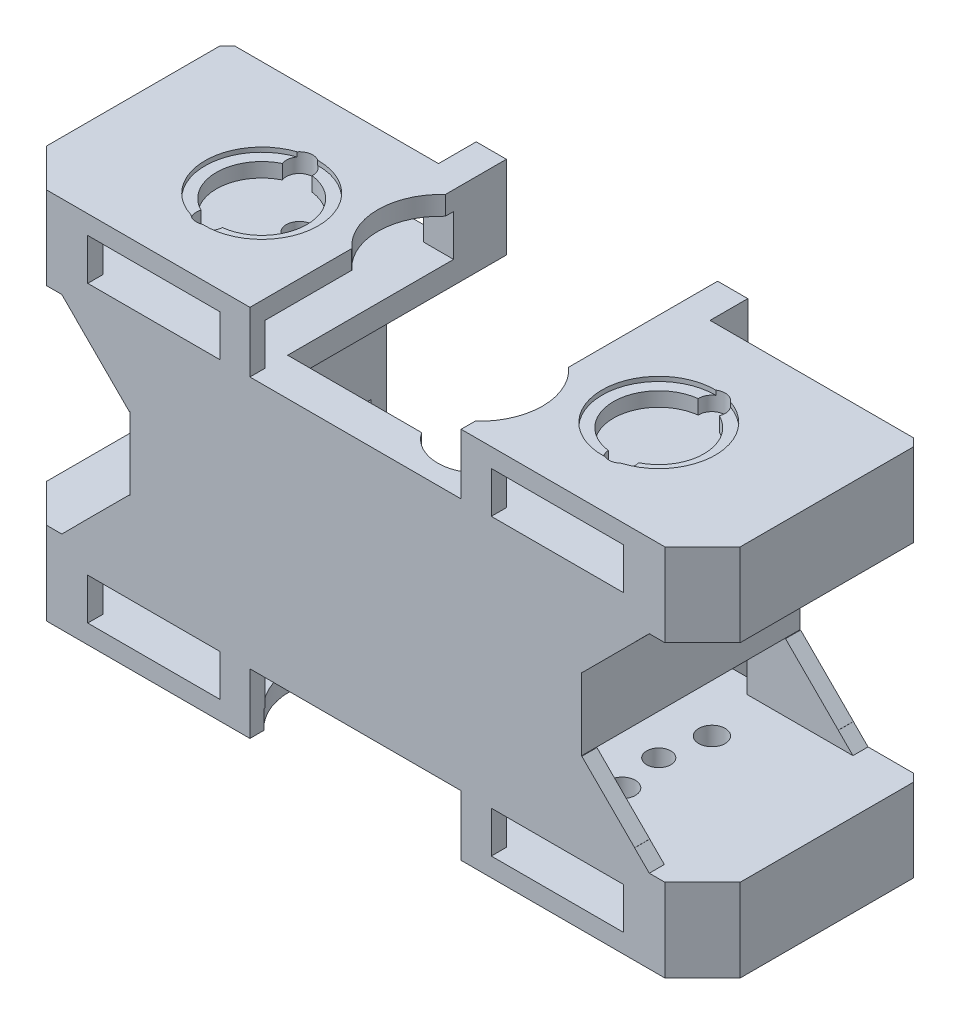
SolidWorks part; units mm, degrees
ref_plane "正面" through (0, 0, 0) normal (0, 0, 1) x (1, 0, 0)
ref_plane "平面" through (0, 0, 0) normal (0, 1, 0) x (1, 0, 0)
ref_plane "右側面" through (0, 0, 0) normal (1, 0, 0) x (0, 0, -1)
sketch "Sketch1" plane through (0, 0, 0) normal (0, 0, 1) x (1, 0, 0)
  line L0 (2.2, -4.75) -> (-2.2, -4.75) construction
  line L2 (-37, 13.75) -> (37, 13.75)
  line L3 (37, -13.75) -> (-37, -13.75)
  line L4 (30.8552, 0) -> (-45.9764, 0) construction
  line L5 (37, -4.795) -> (24.925, -4.795)
  line L6 (24.925, -4.795) -> (24.925, 4.795)
  line L7 (37, 4.795) -> (24.925, 4.795)
  line L8 (0, -7.712) -> (0, 34.8193) construction
  line L11 (-2.2, -4.75) -> (-2.2, 4.75) construction
  line L13 (2.2, -4.75) -> (2.2, 4.75) construction
  line L16 (2.2, 1.8709) -> (2.2, 4.75) construction
  line L17 (2.2, 1.8709) -> (2.2, 4.75) construction
  line L18 (-37, -13.75) -> (-37, -4.795)
  line L22 (-37, 4.795) -> (-24.925, 4.795)
  line L23 (-24.925, -4.795) -> (-24.925, 4.795)
  line L24 (-37, -4.795) -> (-24.925, -4.795)
  line L25 (-37, 4.795) -> (-37, 13.75)
  line L28 (37, 4.795) -> (37, 13.75)
  line L29 (37, -13.75) -> (37, -4.795)
  line L30 (2.2, 4.75) -> (-2.2, 4.75) construction
  point P2 (-2.2, 1.8709)
  point P8 (24.925, 0)
  point P33 (-24.925, 0)
  dimension "D1" = 27.5
  dimension "D2" = 37
  dimension "D3" = 2.2
  dimension "D4" = 4.4
  dimension "D5" = 9.5
extrude "Boss-Extrude1" add sketch "Sketch1" along normal blind 2
sketch "Sketch2" plane through (0, 0, 0) normal (0, 0, -1) x (-1, 0, 0)
  line L0 (-2.2, -4.75) -> (2.2, -4.75) construction
  line L1 (-2.2, -4.75) -> (-2.2, 4.75) construction
  line L2 (-2.2, 4.75) -> (2.2, 4.75) construction
  line L3 (2.2, -4.75) -> (2.2, 4.75) construction
  line L4 (-2.2, -4.75) -> (2.2, -4.75)
  line L5 (-2.2, -4.75) -> (-2.2, 4.75)
  line L6 (-2.2, 4.75) -> (2.2, 4.75)
  line L7 (2.2, -4.75) -> (2.2, 4.75)
  line L8 (37, -4.795) -> (24.925, -4.795) construction
  line L9 (24.925, -4.795) -> (24.925, 4.795) construction
  line L10 (37, 4.795) -> (24.925, 4.795) construction
  line L11 (-37, -4.795) -> (-24.925, -4.795) construction
  line L12 (-24.925, -4.795) -> (-24.925, 4.795) construction
  line L13 (-37, 4.795) -> (-24.925, 4.795) construction
  line L14 (29.925, -4.795) -> (24.925, -4.795)
  line L15 (24.925, -4.795) -> (24.925, 4.795)
  line L16 (29.925, 4.795) -> (24.925, 4.795)
  line L17 (-29.925, -4.795) -> (-24.925, -4.795)
  line L18 (-24.925, -4.795) -> (-24.925, 4.795)
  line L19 (-29.925, 4.795) -> (-24.925, 4.795)
  line L20 (-29.925, 4.795) -> (-29.925, -4.795)
  line L21 (0, -7.712) -> (0, 34.8193) construction
  line L22 (0, -7.712) -> (0, 34.8193) construction
  line L23 (29.925, 4.795) -> (29.925, -4.795)
  dimension "D1" = 5
extrude "Boss-Extrude2" add sketch "Sketch2" along normal blind 25 and the other way blind 2
sketch "Sketch3" plane through (0, 0, 2) normal (0, 0, 1) x (1, 0, 0)
  line L0 (0, -63.6478) -> (0, 57.6808) construction
  line L1 (54.2453, 0) -> (-65.9985, 0) construction
  line L11 (-37, 11.75) -> (-37, 24.75)
  line L12 (-37, 24.75) -> (-14, 24.75)
  line L13 (-14, 24.75) -> (-14, 11.75)
  line L14 (-14, 11.75) -> (-37, 11.75)
  line L19 (-37, 4.795) -> (-37, 13.75) construction
  line L20 (-37, 13.75) -> (37, 13.75) construction
  line L21 (14, 11.75) -> (37, 11.75)
  line L22 (14, 24.75) -> (14, 11.75)
  line L23 (37, 24.75) -> (14, 24.75)
  line L24 (37, 11.75) -> (37, 24.75)
  line L25 (37, -11.75) -> (37, -24.75)
  line L26 (37, -24.75) -> (14, -24.75)
  line L27 (14, -24.75) -> (14, -11.75)
  line L28 (14, -11.75) -> (37, -11.75)
  line L29 (-14, -11.75) -> (-37, -11.75)
  line L30 (-14, -24.75) -> (-14, -11.75)
  line L31 (-37, -24.75) -> (-14, -24.75)
  line L32 (-37, -11.75) -> (-37, -24.75)
  line L33 (-35.5, 22.25) -> (-18, 22.25)
  line L34 (-18, 22.25) -> (-18, 15.75)
  line L35 (-18, 15.75) -> (-35.5, 15.75)
  line L36 (-35.5, 15.75) -> (-35.5, 22.25)
  line L37 (35.5, 15.75) -> (35.5, 22.25)
  line L38 (18, 15.75) -> (35.5, 15.75)
  line L39 (18, 22.25) -> (18, 15.75)
  line L40 (35.5, 22.25) -> (18, 22.25)
  line L41 (35.5, -22.25) -> (18, -22.25)
  line L42 (18, -22.25) -> (18, -15.75)
  line L43 (18, -15.75) -> (35.5, -15.75)
  line L44 (35.5, -15.75) -> (35.5, -22.25)
  line L45 (-35.5, -15.75) -> (-35.5, -22.25)
  line L46 (-18, -15.75) -> (-35.5, -15.75)
  line L47 (-18, -22.25) -> (-18, -15.75)
  line L48 (-35.5, -22.25) -> (-18, -22.25)
  dimension "D1" = 2
  dimension "D2" = 13
  dimension "D3" = 23
  dimension "D4" = 2.5
  dimension "D5" = 4
  dimension "D6" = 4
  dimension "D7" = 1.5
extrude "Boss-Extrude3" add sketch "Sketch3" against normal blind 2
chamfer "Chamfer4" [suppressed] distance 2 angle 45
sketch "Sketch4" plane through (0, 0, 2) normal (0, 0, 1) x (1, 0, 0)
  line L0 (30.8552, 0) -> (-45.9764, 0) construction
  line L1 (0, -7.712) -> (0, 34.8193) construction
  line L2 (30.8552, 0) -> (-45.9764, 0) construction
  line L3 (0, -7.712) -> (0, 34.8193) construction
  line L4 (37, 24.75) -> (14, 24.75)
  line L5 (14, 24.75) -> (14, 22.25)
  line L6 (14, 22.25) -> (37, 22.25)
  line L7 (37, 4.795) -> (37, 24.75) construction
  line L9 (14, 13.75) -> (14, 16.75)
  line L10 (14, 24.75) -> (14, 13.75) construction
  line L12 (-46, 16.75) -> (-46, 13.75)
  line L13 (46, 16.75) -> (46, 13.75)
  line L14 (14, 16.75) -> (46, 16.75)
  line L15 (-14, 13.75) -> (-14, 16.75)
  line L17 (-14, 22.25) -> (-37, 22.25)
  line L18 (-14, 24.75) -> (-14, 22.25)
  line L19 (-37, 24.75) -> (-14, 24.75)
  line L20 (-14, 13.75) -> (-14, 24.75) construction
  line L21 (37, 22.25) -> (37, 24.75)
  line L22 (-37, 22.25) -> (-37, 24.75)
  line L23 (-37, -22.25) -> (-37, -24.75)
  line L24 (37, -22.25) -> (37, -24.75)
  line L25 (-37, -24.75) -> (-14, -24.75)
  line L26 (-14, -24.75) -> (-14, -22.25)
  line L27 (-14, -22.25) -> (-37, -22.25)
  line L29 (-14, -13.75) -> (-14, -16.75)
  line L30 (14, -16.75) -> (46, -16.75)
  line L31 (46, -16.75) -> (46, -13.75)
  line L32 (-46, -16.75) -> (-46, -13.75)
  line L33 (-14, -16.75) -> (-46, -16.75)
  line L34 (14, -13.75) -> (14, -16.75)
  line L36 (14, -22.25) -> (37, -22.25)
  line L37 (14, -24.75) -> (14, -22.25)
  line L38 (37, -24.75) -> (14, -24.75)
  line L39 (-14, 16.75) -> (-46, 16.75)
  line L40 (-46, 13.75) -> (-14, 13.75)
  line L41 (-46, -13.75) -> (-14, -13.75)
  line L42 (14, -13.75) -> (46, -13.75)
  line L43 (14, 13.75) -> (46, 13.75)
  dimension "D1" = 32
  dimension "D2" = 3
  dimension "D3" = 2.5
extrude "Boss-Extrude4" add sketch "Sketch4" against normal blind 27
sketch "Sketch5" plane through (0, 0, -25) normal (0, 0, -1) x (-1, 0, 0)
  line L85 (14, -13.75) -> (14, -24.75)
  line L86 (-14, -13.75) -> (14, -13.75)
  line L87 (-14, -24.75) -> (-14, -13.75)
  line L88 (-37, -24.75) -> (-14, -24.75)
  line L89 (-37, -16.75) -> (-37, -24.75)
  line L90 (-29.925, -4.795) -> (-37, -4.795)
  line L91 (-29.925, 4.795) -> (-29.925, -4.795)
  line L92 (-37, 4.795) -> (-29.925, 4.795)
  line L93 (-37, 13.75) -> (-37, 4.795)
  line L94 (-14, 24.75) -> (-37, 24.75)
  line L95 (-14, 13.75) -> (-14, 24.75)
  line L96 (14, 13.75) -> (-14, 13.75)
  line L97 (14, 24.75) -> (14, 13.75)
  line L98 (37, 24.75) -> (14, 24.75)
  line L99 (37, 16.75) -> (37, 24.75)
  line L100 (29.925, 4.795) -> (37, 4.795)
  line L101 (29.925, -4.795) -> (29.925, 4.795)
  line L102 (37, -4.795) -> (29.925, -4.795)
  line L103 (37, -13.75) -> (37, -4.795)
  line L104 (14, -24.75) -> (37, -24.75)
  line L105 (14, -13.75) -> (14, -24.75)
  line L106 (-14, -13.75) -> (14, -13.75)
  line L107 (-14, -24.75) -> (-14, -13.75)
  line L108 (-37, -24.75) -> (-14, -24.75)
  line L109 (-37, -16.75) -> (-37, -24.75)
  line L110 (-29.925, -4.795) -> (-37, -4.795)
  line L111 (-29.925, 4.795) -> (-29.925, -4.795)
  line L112 (-37, 4.795) -> (-29.925, 4.795)
  line L113 (-37, 13.75) -> (-37, 4.795)
  line L114 (-14, 24.75) -> (-37, 24.75)
  line L115 (-14, 13.75) -> (-14, 24.75)
  line L116 (14, 13.75) -> (-14, 13.75)
  line L117 (14, 24.75) -> (14, 13.75)
  line L118 (37, 24.75) -> (14, 24.75)
  line L119 (37, 16.75) -> (37, 24.75)
  line L120 (29.925, 4.795) -> (37, 4.795)
  line L121 (29.925, -4.795) -> (29.925, 4.795)
  line L122 (37, -4.795) -> (29.925, -4.795)
  line L123 (37, -13.75) -> (37, -4.795)
  line L124 (14, -24.75) -> (37, -24.75)
  line L141 (-46, -16.75) -> (-37, -16.75)
  line L142 (-46, -16.75) -> (-37, -16.75)
  line L143 (-46, -13.75) -> (-46, -16.75)
  line L144 (-46, -13.75) -> (-46, -16.75)
  line L145 (-37, -13.75) -> (-46, -13.75)
  line L146 (-37, -13.75) -> (-46, -13.75)
  line L147 (-37, -4.795) -> (-37, -13.75)
  line L148 (-37, -4.795) -> (-37, -13.75)
  line L149 (-46, 13.75) -> (-37, 13.75)
  line L150 (-46, 13.75) -> (-37, 13.75)
  line L151 (-46, 16.75) -> (-46, 13.75)
  line L152 (-46, 16.75) -> (-46, 13.75)
  line L153 (-37, 16.75) -> (-46, 16.75)
  line L154 (-37, 16.75) -> (-46, 16.75)
  line L155 (-37, 24.75) -> (-37, 16.75)
  line L156 (-37, 24.75) -> (-37, 16.75)
  line L157 (46, 16.75) -> (37, 16.75)
  line L158 (46, 16.75) -> (37, 16.75)
  line L159 (46, 13.75) -> (46, 16.75)
  line L160 (46, 13.75) -> (46, 16.75)
  line L161 (37, 13.75) -> (46, 13.75)
  line L162 (37, 13.75) -> (46, 13.75)
  line L163 (37, 4.795) -> (37, 13.75)
  line L164 (37, 4.795) -> (37, 13.75)
  line L165 (46, -13.75) -> (37, -13.75)
  line L166 (46, -13.75) -> (37, -13.75)
  line L167 (46, -16.75) -> (46, -13.75)
  line L168 (46, -16.75) -> (46, -13.75)
  line L169 (37, -16.75) -> (46, -16.75)
  line L170 (37, -16.75) -> (46, -16.75)
  line L171 (37, -24.75) -> (37, -16.75)
  line L172 (37, -24.75) -> (37, -16.75)
  dimension "D1" = 0
extrude "Boss-Extrude5" add sketch "Sketch5" along normal blind 2
chamfer "Chamfer5" distance 5 angle 45 4 edges at (46, -15.25, 2) (46, 15.25, 2) (-46, -15.25, 2) (-46, 15.25, 2)
chamfer "Chamfer6" distance 7 angle 45 8 edges at (-37, 4.795, 1) (-37, -4.795, 1) (-37, -4.795, -26) (-37, 4.795, -26) (37, 4.795, -26) (37, -4.795, -26) (37, -4.795, 1) (37, 4.795, 1)
sketch "Sketch6" plane through (0, 16.75, 0) normal (0, 1, 0) x (1, 0, 0)
  line L2 (-46, 27) -> (-46, 3) construction
  line L3 (-46, 27) -> (-37, 27) construction
  line L4 (-37, 0) -> (-37, -2)
  line L6 (-46, 27) -> (-46, 3)
  line L7 (-46, 27) -> (-37, 27)
  line L9 (-37, 27) -> (-37, 25)
  line L10 (-37, 25) -> (-44, 25)
  line L11 (-44, 25) -> (-44, 3.8284)
  line L13 (0, 37.9752) -> (0, -9.1121) construction
  line L22 (-46, 3) -> (-41, -2)
  line L23 (-41, -2) -> (-37, -2)
  line L25 (-44, 3.8284) -> (-40.1716, 0)
  line L26 (-40.1716, 0) -> (-37, 0)
  line L27 (-37, 0) -> (-35.5, 0) construction
  line L38 (-37, 27) -> (-37, -2) construction
  line L39 (40.1716, 0) -> (37, 0)
  line L40 (44, 3.8284) -> (40.1716, 0)
  line L41 (41, -2) -> (37, -2)
  line L42 (46, 3) -> (41, -2)
  line L43 (44, 25) -> (44, 3.8284)
  line L44 (37, 25) -> (44, 25)
  line L45 (37, 27) -> (37, 25)
  line L46 (46, 27) -> (37, 27)
  line L47 (46, 27) -> (46, 3)
  line L48 (37, 0) -> (37, -2)
  dimension "D1" = 2
  dimension "D2" = 2
  dimension "D3" = 2
extrude "Boss-Extrude6" add sketch "Sketch6" along normal up to surface (5.5 mm away) up to face at (-26.125, 22.25, -5.75)
sketch "Sketch7" plane through (0, 22.25, 0) normal (0, 1, 0) x (1, 0, 0)
  line L1 (-46, 3) -> (-46, 27) construction
  line L2 (-46, 27) -> (-37, 27) construction
  line L3 (-37, 27) -> (-37, -2) construction
  line L9 (-46, 3) -> (-46, 27)
  line L10 (-46, 27) -> (-37, 27)
  line L11 (-37, 27) -> (-37, -2)
  line L16 (-41, -2) -> (-37, -2) construction
  line L17 (-46, 3) -> (-41, -2) construction
  line L18 (-41, -2) -> (-37, -2)
  line L19 (-46, 3) -> (-41, -2)
  line L20 (0, 40.7113) -> (0, -15.6848) construction
  line L21 (46, 3) -> (41, -2)
  line L22 (41, -2) -> (37, -2)
  line L23 (37, 27) -> (37, -2)
  line L24 (46, 27) -> (37, 27)
  line L25 (46, 3) -> (46, 27)
extrude "Boss-Extrude7" add sketch "Sketch7" along normal up to surface (2.5 mm away) up to face at (-25.5, 24.75, -12.5)
sketch "Sketch8" plane through (0, 0, -25) normal (0, 0, 1) x (1, 0, 0)
  line L3 (-18, 16.75) -> (-18, 22.25)
  line L4 (-14, 16.75) -> (-14, 22.25)
  line L5 (-14, 22.25) -> (-44, 22.25)
  line L6 (-44, 22.25) -> (-44, 16.75)
  line L7 (-44, 16.75) -> (-14, 16.75)
  line L9 (-18, 22.25) -> (-44, 22.25)
  line L10 (-44, 22.25) -> (-44, 16.75)
  line L11 (-44, 16.75) -> (-18, 16.75)
  line L12 (14, 16.75) -> (44, 16.75)
  line L13 (44, 16.75) -> (44, 22.25)
  line L14 (44, 22.25) -> (14, 22.25)
  line L15 (14, 22.25) -> (14, 16.75)
  line L16 (18, 16.75) -> (44, 16.75)
  line L17 (44, 16.75) -> (44, 22.25)
  line L18 (44, 22.25) -> (18, 22.25)
  line L20 (18, 22.25) -> (18, 16.75)
  line L21 (18, 22.25) -> (18, 16.75) construction
  line L22 (30.8552, 0) -> (-45.9764, 0) construction
  line L23 (30.8552, 0) -> (-45.9764, 0) construction
  dimension "D1" = 0
  dimension "D2" = 0
extrude "Cut-Extrude1" cut sketch "Sketch8" against normal through all
sketch "Sketch9" plane through (0, -16.75, 0) normal (0, -1, 0) x (1, 0, 0)
  line L10 (41, 2) -> (37, 2)
  line L11 (37, 2) -> (37, 0)
  line L12 (37, 0) -> (40.1716, 0)
  line L13 (40.1716, 0) -> (44, -3.8284)
  line L14 (44, -3.8284) -> (44, -25)
  line L15 (44, -25) -> (37, -25)
  line L16 (37, -25) -> (37, -27)
  line L17 (37, -27) -> (46, -27)
  line L18 (46, -27) -> (46, -3)
  line L19 (46, -3) -> (41, 2)
  line L20 (41, 2) -> (37, 2)
  line L21 (37, 2) -> (37, 0)
  line L22 (37, 0) -> (40.1716, 0)
  line L23 (40.1716, 0) -> (44, -3.8284)
  line L24 (44, -3.8284) -> (44, -25)
  line L25 (44, -25) -> (37, -25)
  line L26 (37, -25) -> (37, -27)
  line L27 (37, -27) -> (46, -27)
  line L28 (46, -27) -> (46, -3)
  line L29 (46, -3) -> (41, 2)
  line L30 (-41, 2) -> (-46, -3)
  line L31 (-46, -3) -> (-46, -27)
  line L32 (-46, -27) -> (-37, -27)
  line L33 (-37, -27) -> (-37, -25)
  line L34 (-37, -25) -> (-44, -25)
  line L35 (-44, -25) -> (-44, -3.8284)
  line L36 (-44, -3.8284) -> (-40.1716, 0)
  line L37 (-40.1716, 0) -> (-37, 0)
  line L38 (-37, 0) -> (-37, 2)
  line L39 (-37, 2) -> (-41, 2)
  line L40 (-41, 2) -> (-46, -3)
  line L41 (-46, -3) -> (-46, -27)
  line L42 (-46, -27) -> (-37, -27)
  line L43 (-37, -27) -> (-37, -25)
  line L44 (-37, -25) -> (-44, -25)
  line L45 (-44, -25) -> (-44, -3.8284)
  line L46 (-44, -3.8284) -> (-40.1716, 0)
  line L47 (-40.1716, 0) -> (-37, 0)
  line L48 (-37, 0) -> (-37, 2)
  line L49 (-37, 2) -> (-41, 2)
  dimension "D1" = 0
  dimension "D2" = 0
extrude "Boss-Extrude8" add sketch "Sketch9" along normal up to surface (5.5 mm away) up to face at (26.125, -22.25, -5.75)
sketch "Sketch10" plane through (0, -22.25, 0) normal (0, -1, 0) x (1, 0, 0)
  line L5 (46, -3) -> (41, 2)
  line L6 (41, 2) -> (37, 2)
  line L7 (37, 2) -> (37, -27)
  line L8 (37, -27) -> (46, -27)
  line L9 (46, -27) -> (46, -3)
  line L10 (46, -3) -> (41, 2)
  line L11 (41, 2) -> (37, 2)
  line L12 (37, 2) -> (37, -27)
  line L13 (37, -27) -> (46, -27)
  line L14 (46, -27) -> (46, -3)
  line L15 (-46, -3) -> (-46, -27)
  line L16 (-46, -27) -> (-37, -27)
  line L17 (-37, -27) -> (-37, 2)
  line L18 (-37, 2) -> (-41, 2)
  line L19 (-41, 2) -> (-46, -3)
  line L20 (-46, -3) -> (-46, -27)
  line L21 (-46, -27) -> (-37, -27)
  line L22 (-37, -27) -> (-37, 2)
  line L23 (-37, 2) -> (-41, 2)
  line L24 (-41, 2) -> (-46, -3)
  dimension "D1" = 0
  dimension "D2" = 0
extrude "Boss-Extrude9" add sketch "Sketch10" along normal up to surface (2.5 mm away) up to face at (25.5, -24.75, -12.5)
sketch "Sketch11" plane through (0, 0, -27) normal (0, 0, -1) x (-1, 0, 0)
  line L0 (-56.3853, 0) -> (62.7444, 0) construction
  line L1 (18, -16.75) -> (44, -16.75)
  line L2 (44, -16.75) -> (44, -22.25)
  line L3 (44, -22.25) -> (18, -22.25)
  line L4 (-44, 16.75) -> (-18, 16.75)
  line L5 (-44, 22.25) -> (-44, 16.75)
  line L6 (-18, 22.25) -> (-44, 22.25)
  line L7 (-18, 16.75) -> (-18, 22.25)
  line L8 (-44, 16.75) -> (-18, 16.75) construction
  line L9 (-44, 22.25) -> (-44, 16.75) construction
  line L10 (-18, 22.25) -> (-44, 22.25) construction
  line L11 (-18, 16.75) -> (-18, 22.25) construction
  line L12 (18, 22.25) -> (18, 16.75)
  line L13 (44, 22.25) -> (18, 22.25)
  line L14 (44, 16.75) -> (44, 22.25)
  line L15 (18, 16.75) -> (44, 16.75)
  line L16 (18, 22.25) -> (18, 16.75) construction
  line L17 (44, 22.25) -> (18, 22.25) construction
  line L18 (44, 16.75) -> (44, 22.25) construction
  line L19 (18, 16.75) -> (44, 16.75) construction
  line L20 (18, -22.25) -> (18, -16.75)
  line L21 (-18, -16.75) -> (-18, -22.25)
  line L22 (-18, -22.25) -> (-44, -22.25)
  line L23 (-44, -22.25) -> (-44, -16.75)
  line L24 (-44, -16.75) -> (-18, -16.75)
  dimension "D1" = 0
  dimension "D2" = 0
extrude "Cut-Extrude2" cut sketch "Sketch11" against normal blind 2
sketch "Sketch12" plane through (0, -4.75, 0) normal (0, -1, 0) x (1, 0, 0)
  circle A0 centre (-0.16, -17.91) radius 0.75
  circle A1 centre (0.16, -6) radius 0.75
  dimension "D1" = 1.5
  dimension "D2" = 1.5
extrude "Cut-Extrude3" cut sketch "Sketch12" against normal blind 5
sketch "Sketch13" plane through (0, 4.75, 0) normal (0, 1, 0) x (1, 0, 0)
  circle A0 centre (0.16, 6) radius 0.75 construction
  circle A1 centre (-0.16, 17.91) radius 0.75 construction
  circle A2 centre (0.16, 6) radius 0.75
  circle A3 centre (-0.16, 17.91) radius 0.75
extrude "Cut-Extrude4" cut sketch "Sketch13" against normal blind 5
chamfer "Chamfer7" distance 1.94 angle 45 8 edges at (-37, -13.75, 1) (-37, -13.75, -26) (-37, 13.75, -26) (-37, 13.75, 1) (37, -13.75, -26) (37, -13.75, 1) (37, 13.75, 1) (37, 13.75, -26)
sketch "Sketch14" plane through (0, 4.795, 0) normal (0, 1, 0) x (1, 0, 0)
  line L1 (0, 37.5677) -> (0, -8.4174) construction
  circle A0 centre (27.34, 6) radius 0.75
  circle A1 centre (27.34, 17.91) radius 0.75
  circle A2 centre (-27.34, 17.91) radius 0.75
  circle A3 centre (-27.34, 6) radius 0.75
  dimension "D1" = 1.5
  dimension "D2" = 1.5
extrude "Cut-Extrude5" cut sketch "Sketch14" against normal blind 5
sketch "Sketch15" plane through (0, -4.795, 0) normal (0, -1, 0) x (1, 0, 0)
  line L0 (0, -39.3309) -> (0, 8.4378) construction
  circle A0 centre (27.34, -17.91) radius 0.75 construction
  circle A1 centre (27.34, -6) radius 0.75 construction
  circle A2 centre (27.34, -17.91) radius 0.75
  circle A3 centre (27.34, -6) radius 0.75
  circle A4 centre (-27.34, -6) radius 0.75
  circle A5 centre (-27.34, -17.91) radius 0.75
extrude "Cut-Extrude6" cut sketch "Sketch15" against normal blind 5
sketch "Sketch16" plane through (0, 24.75, 0) normal (0, 1, 0) x (1, 0, 0)
  line L0 (0, 40.1224) -> (0, 0) construction
  circle A0 centre (-27.34, 17.91) radius 0.75 construction
  circle A1 centre (-27.34, 6) radius 0.75 construction
  circle A2 centre (-27.34, 17.91) radius 0.75 construction
  circle A3 centre (-27.34, 6) radius 0.75 construction
  circle A4 centre (27.34, 6) radius 0.75 construction
  circle A5 centre (27.34, 17.91) radius 0.75 construction
  circle A6 centre (27.34, 17.91) radius 1.75
  circle A9 centre (27.34, 6) radius 1.75
  circle A10 centre (-27.34, 6) radius 1.75
  circle A11 centre (-27.34, 17.91) radius 1.75
  dimension "D1" = 3.5
  dimension "D2" = 3.5
extrude "Cut-Extrude7" cut sketch "Sketch16" against normal up to surface (11 mm away) up to face at (-35.1956, 13.75, -11.4444)
sketch "Sketch17" plane through (0, -24.75, 0) normal (0, -1, 0) x (1, 0, 0)
  circle A0 centre (27.34, -6) radius 1.75 construction
  circle A1 centre (27.34, -17.91) radius 1.75 construction
  circle A2 centre (-27.34, -6) radius 1.75 construction
  circle A3 centre (-27.34, -17.91) radius 1.75 construction
  circle A4 centre (27.34, -6) radius 1.75
  circle A5 centre (27.34, -17.91) radius 1.75
  circle A6 centre (-27.34, -6) radius 1.75
  circle A7 centre (-27.34, -17.91) radius 1.75
extrude "Cut-Extrude8" cut sketch "Sketch17" against normal up to surface (11 mm away) up to face at (-35.1956, -13.75, -11.4444)
sketch "Sketch18" plane through (0, 0, -25) normal (0, 0, 1) x (1, 0, 0)
  line L0 (-24.925, 0) -> (-24.925, -13.75)
  line L1 (-24.925, -13.75) -> (24.925, -13.75)
  line L2 (24.925, -13.75) -> (24.925, 13.75)
  line L3 (24.925, 13.75) -> (-24.925, 13.75)
  line L4 (-24.925, 13.75) -> (-24.925, 0)
  line L5 (-24.925, -4.795) -> (-24.925, 4.795) construction
  line L7 (14, -13.75) -> (-14, -13.75) construction
  line L8 (14, -13.75) -> (-14, -13.75) construction
  line L10 (37, -13.75) -> (-37, -13.75) construction
  line L11 (24.925, -4.795) -> (24.925, 4.795) construction
  line L12 (-37, 13.75) -> (37, 13.75) construction
extrude "Cut-Extrude9" cut sketch "Sketch18" against normal through all
sketch "Sketch19" plane through (0, 24.75, 0) normal (0, 1, 0) x (1, 0, 0)
  line L0 (0, 42.42) -> (0, 6.5011) construction
  line L1 (0, 42.42) -> (0, 6.5011) construction
  circle A0 centre (26.32, 11.88) radius 6
  circle A1 centre (-26.32, 11.88) radius 6
  dimension "D1" = 12
extrude "Cut-Extrude10" cut sketch "Sketch19" against normal blind 5
sketch "Sketch20" plane through (0, -24.75, 0) normal (0, -1, 0) x (1, 0, 0)
  circle A1 centre (-26.32, -11.88) radius 6
  circle A2 centre (-26.32, -11.88) radius 6
  circle A3 centre (26.32, -11.88) radius 6
  circle A4 centre (26.32, -11.88) radius 6
  dimension "D1" = 0
  dimension "D2" = 0
extrude "Cut-Extrude11" cut sketch "Sketch20" against normal blind 5
sketch "Sketch21" plane through (0, 16.75, 0) normal (0, 1, 0) x (1, 0, 0)
  circle A0 centre (-26.32, 11.88) radius 1.6
  circle A1 centre (26.32, 11.88) radius 1.6
  dimension "D1" = 3.2
  dimension "D2" = 3.2
extrude "Cut-Extrude12" cut sketch "Sketch21" against normal blind 5
sketch "Sketch22" plane through (0, -16.75, 0) normal (0, -1, 0) x (1, 0, 0)
  circle A1 centre (26.32, -11.88) radius 1.6
  circle A2 centre (26.32, -11.88) radius 1.6
  circle A3 centre (-26.32, -11.88) radius 1.6
  circle A4 centre (-26.32, -11.88) radius 1.6
  dimension "D1" = 0
  dimension "D2" = 0
extrude "Cut-Extrude13" cut sketch "Sketch22" against normal blind 5
sketch "Sketch23" plane through (0, 0, -27) normal (0, 0, -1) x (-1, 0, 0)
  line L0 (18, 16.75) -> (18, 16.25)
  line L1 (18, 16.25) -> (44, 16.25)
  line L2 (44, 16.25) -> (44, 16.75)
  line L3 (44, 16.75) -> (18, 16.75)
  line L4 (44, 22.25) -> (44, 16.75) construction
  line L5 (0, -7.712) -> (0, 34.8193) construction
  line L6 (-30.8552, 0) -> (45.9764, 0) construction
  line L7 (0, -7.712) -> (0, 34.8193) construction
  line L8 (-30.8552, 0) -> (45.9764, 0) construction
  line L9 (-44, 16.75) -> (-18, 16.75)
  line L10 (-44, 16.25) -> (-44, 16.75)
  line L11 (-18, 16.25) -> (-44, 16.25)
  line L12 (-18, 16.75) -> (-18, 16.25)
  line L13 (-18, -16.75) -> (-18, -16.25)
  line L14 (-18, -16.25) -> (-44, -16.25)
  line L15 (-44, -16.25) -> (-44, -16.75)
  line L16 (-44, -16.75) -> (-18, -16.75)
  line L17 (44, -16.75) -> (18, -16.75)
  line L18 (44, -16.25) -> (44, -16.75)
  line L19 (18, -16.25) -> (44, -16.25)
  line L20 (18, -16.75) -> (18, -16.25)
  dimension "D1" = 0.5
extrude "Cut-Extrude14" [suppressed] cut sketch "Sketch23" against normal blind 23
sketch "Sketch24" plane through (0, 24.75, 0) normal (0, 1, 0) x (1, 0, 0)
  circle A0 centre (26.32, 11.88) radius 7.5
  circle A1 centre (-26.32, 11.88) radius 7.5
  dimension "D1" = 15
  dimension "D2" = 15
extrude "Cut-Extrude15" cut sketch "Sketch24" against normal blind 0.6
sketch "Sketch25" plane through (0, -24.75, 0) normal (0, -1, 0) x (1, 0, 0)
  circle A1 centre (-26.32, -11.88) radius 7.5
  circle A2 centre (-26.32, -11.88) radius 7.5
  circle A3 centre (26.32, -11.88) radius 7.5
  circle A4 centre (26.32, -11.88) radius 7.5
  dimension "D1" = 0
  dimension "D2" = 0
extrude "Cut-Extrude16" cut sketch "Sketch25" against normal blind 0.6
sketch "Sketch26" plane through (0, 0, -27) normal (0, 0, -1) x (-1, 0, 0)
  line L0 (37, 16.75) -> (37, 14.75)
  line L1 (44, 16.75) -> (18, 16.75) construction
  line L2 (37, 14.75) -> (35, 14.75)
  line L3 (35, 14.75) -> (35, 16.75)
  line L4 (35, 16.75) -> (37, 16.75)
  line L5 (38, 16.75) -> (38, 14.75)
  line L7 (38, 14.75) -> (40, 14.75)
  line L8 (40, 14.75) -> (40, 16.75)
  line L9 (40, 16.75) -> (38, 16.75)
  line L10 (46, 13.75) -> (46, 24.75) construction
  dimension "D1" = 1
  dimension "D2" = 2
  dimension "D3" = 2
  dimension "D4" = 2
  dimension "D5" = 2
  dimension "D6" = 6
extrude "Boss-Extrude10" [suppressed] add sketch "Sketch26" along normal blind 5
sketch "Sketch27" [suppressed] plane through (0, 0, -27) normal (0, 0, -1) x (-1, 0, 0)
  line L0 (37, -16.75) -> (37, -13.75)
  line L1 (44, -16.75) -> (18, -16.75) construction
  line L2 (37, -13.75) -> (38, -13.75)
  line L3 (38, -13.75) -> (38, -16.75)
  line L4 (35.5, -16.75) -> (40.1716, -16.75) construction
  line L5 (38, -16.75) -> (37, -16.75)
  line L6 (37, 16.75) -> (37, 14.75)
  line L7 (37, 14.75) -> (38, 14.75)
  line L8 (38, 14.75) -> (38, 16.75)
  line L9 (38, 16.75) -> (37, 16.75)
  dimension "D1" = 1
  dimension "D2" = 3
extrude "Boss-Extrude11" [suppressed] add sketch "Sketch27" along normal blind 3
chamfer "Chamfer8" [suppressed] distance 3 angle 45
sketch "Sketch28" plane through (0, 0, -27) normal (0, 0, -1) x (-1, 0, 0)
  line L0 (0, 36.1152) -> (0, -30.2871) construction
  line L1 (-14, 13.75) -> (-18, 13.75)
  line L3 (-18, 13.75) -> (-18, 24.75)
  line L4 (-14, 24.75) -> (-46, 24.75) construction
  line L5 (-18, 24.75) -> (-14, 24.75)
  line L6 (-14, 24.75) -> (-14, 13.75)
  line L7 (14, 24.75) -> (14, 13.75)
  line L8 (18, 24.75) -> (14, 24.75)
  line L9 (18, 13.75) -> (18, 24.75)
  line L10 (14, 13.75) -> (18, 13.75)
  line L11 (-36.9089, 0) -> (45.8109, 0) construction
  line L12 (14, -13.75) -> (18, -13.75)
  line L13 (18, -13.75) -> (18, -24.75)
  line L14 (18, -24.75) -> (14, -24.75)
  line L15 (14, -24.75) -> (14, -13.75)
  line L16 (-14, -24.75) -> (-14, -13.75)
  line L17 (-18, -24.75) -> (-14, -24.75)
  line L18 (-18, -13.75) -> (-18, -24.75)
  line L19 (-14, -13.75) -> (-18, -13.75)
  line L20 (14, -13.75) -> (18, -13.75)
  line L21 (18, -13.75) -> (18, -24.75)
  line L22 (18, -24.75) -> (14, -24.75)
  line L23 (14, -24.75) -> (14, -13.75)
  line L24 (-14, -24.75) -> (-14, -13.75)
  line L25 (-18, -24.75) -> (-14, -24.75)
  line L26 (-18, -13.75) -> (-18, -24.75)
  line L27 (-14, -13.75) -> (-18, -13.75)
  line L28 (-24.925, 6) -> (-27.425, 6) construction
  line L29 (-24.925, -13.75) -> (-24.925, 13.75) construction
  line L30 (-27.425, 6) -> (-27.425, -6) construction
  line L31 (-24.925, 6) -> (-24.925, -6) construction
  line L32 (-24.925, -6) -> (-27.425, -6) construction
  point P32 (-24.925, 0)
  point P33 (-27.425, 0)
  line M7 (-14, -13.75) -> (-24.925, -13.75)
  line M9 (-24.925, 13.75) -> (-14, 13.75)
  line M10 (-14, 13.75) -> (-14, 24.75)
  line M11 (-14, 24.75) -> (-46, 24.75)
  line M23 (-46, -24.75) -> (-14, -24.75)
  line M24 (-14, -24.75) -> (-14, -13.75)
  line M26 (-18, -16.75) -> (-18, -22.25)
  line M31 (-18, 22.25) -> (-18, 16.75)
  dimension "D1" = 4
  dimension "D2" = 27.5
  dimension "D3" = 12
  dimension "D4" = 2.5
extrude "Boss-Extrude12" add sketch "Sketch28" along normal blind 5 contours L3 M9 M10 M11 M31 | L7 L10 L9 L8 | L15 L14 L13 L12 | L18 M7 M26 M23 M24 | L31 L32 L30 L28 region at (16, 19.25, -27) region at (-16, 19.25, -27) region at (-16, -19.25, -27) region at (16, -19.25, -27)
sketch "Sketch29" plane through (0, 0, -32) normal (0, 0, -1) x (-1, 0, 0)
  line L0 (0, 27.5164) -> (0, -23.5036) construction
  line L1 (-40.3191, 0) -> (37.835, 0) construction
  line L2 (-14, 13.75) -> (-14, 24.75) construction
  line L4 (-38.94, 13.75) -> (-14, 13.75) construction
  circle A0 centre (-16, 19.75) radius 0.75
  circle A1 centre (16, 19.75) radius 0.75
  circle A2 centre (16, -19.75) radius 0.75
  circle A3 centre (-16, -19.75) radius 0.75
  dimension "D1" = 1.5
  dimension "D2" = 2
  dimension "D3" = 6
extrude "Cut-Extrude17" cut sketch "Sketch29" against normal blind 5
fillet "Fillet1" [suppressed] radius 2
chamfer "Chamfer9" distance 3 angle 45 4 edges at (-14, -13.75, 1) (14, -13.75, 1) (14, 13.75, 1) (-14, 13.75, 1)
chamfer "Chamfer10" distance 1 angle 45 4 edges at (46, 19.25, -27) (46, -19.25, -27) (-46, 19.25, -27) (-46, -19.25, -27)
sketch "Sketch30" plane through (0, 0, -25) normal (0, 0, -1) x (-1, 0, 0)
  line L4 (-2.2, 4.75) -> (-2.2, -4.75)
  line L5 (-2.2, -4.75) -> (2.2, -4.75)
  line L6 (2.2, -4.75) -> (2.2, 4.75)
  line L7 (2.2, 4.75) -> (-2.2, 4.75)
  line L8 (-2.2, 4.75) -> (-2.2, -4.75)
  line L9 (-2.2, -4.75) -> (2.2, -4.75)
  line L10 (2.2, -4.75) -> (2.2, 4.75)
  line L11 (2.2, 4.75) -> (-2.2, 4.75)
  dimension "D1" = 0
extrude "Cut-Extrude18" cut sketch "Sketch30" against normal blind 1
sketch "Sketch31" plane through (0, -24.75, 0) normal (0, -1, 0) x (1, 0, 0)
  line L0 (0, -44.5092) -> (0, 18.2289) construction
  line L1 (-26.32, -11.88) -> (26.32, -11.88) construction
  arc A0 (0, -5.0528) -> (0, -7.0572) centre (-8.34, -6.055) ccw
  arc A1 (0, -5.0528) -> (0, -7.0572) centre (8.34, -6.055) cw construction
  arc A2 (0, -18.7072) -> (0, -16.7028) centre (8.34, -17.705) ccw
  arc A3 (0, -5.0528) -> (0, -7.0572) centre (-8.34, -6.055) cw
  arc A4 (0, -16.7028) -> (0, -18.7072) centre (8.34, -17.705) ccw
  dimension "D1" = 16.8
extrude "Cut-Extrude19" cut sketch "Sketch31" against normal up to surface (2.5 mm away) up to face at (26.9777, -22.25, -11.9241)
sketch "Sketch32" plane through (0, 24.75, 0) normal (0, 1, 0) x (1, 0, 0)
  line L0 (-26.32, 11.88) -> (26.32, 11.88) construction
  line L1 (0, 0) -> (0, 37.2322) construction
  arc A0 (0, 18.7072) -> (0, 16.7028) centre (-8.34, 17.705) cw
  arc A1 (0, 16.7028) -> (0, 18.7072) centre (-8.34, 17.705) cw
  arc A2 (0, 7.0572) -> (0, 5.0528) centre (-8.34, 6.055) ccw
  arc A3 (0, 5.0528) -> (0, 7.0572) centre (-8.34, 6.055) ccw
  arc A4 (0, 7.0572) -> (0, 5.0528) centre (-8.34, 6.055) ccw construction
  arc A6 (0, 5.0528) -> (0, 7.0572) centre (-8.34, 6.055) ccw construction
  arc A7 (0, 7.0572) -> (0, 5.0528) centre (8.34, 6.055) cw
  arc A8 (0, 5.0528) -> (0, 7.0572) centre (8.34, 6.055) cw
  dimension "D1" = 0
extrude "Cut-Extrude20" cut sketch "Sketch32" against normal up to surface (2.5 mm away) up to face at (-26.9777, 22.25, -11.9241)
sketch "Sketch33" plane through (0, 0, -24) normal (0, 0, -1) x (-1, 0, 0)
  line L4 (2.2, 4.75) -> (-2.2, 4.75)
  line L5 (-2.2, 4.75) -> (-2.2, -4.75)
  line L6 (-2.2, -4.75) -> (2.2, -4.75)
  line L7 (2.2, -4.75) -> (2.2, 4.75)
  line L8 (2.2, 4.75) -> (-2.2, 4.75)
  line L9 (-2.2, 4.75) -> (-2.2, -4.75)
  line L10 (-2.2, -4.75) -> (2.2, -4.75)
  line L11 (2.2, -4.75) -> (2.2, 4.75)
  dimension "D1" = 0
extrude "Cut-Extrude21" cut sketch "Sketch33" against normal up to surface (24 mm away) up to face at (0, 0, 0)
sketch "Sketch34" plane through (0, 0, 0) normal (0, 0, -1) x (-1, 0, 0)
  line L0 (-14, 16.75) -> (-14, 13.75)
  line L1 (-14, 13.75) -> (14, 13.75)
  line L2 (14, 13.75) -> (14, 16.75)
  line L3 (14, 16.75) -> (-14, 16.75)
  line L4 (-38.0961, 0) -> (34.0567, 0) construction
  line L5 (14, -16.75) -> (-14, -16.75)
  line L6 (14, -13.75) -> (14, -16.75)
  line L7 (-14, -13.75) -> (14, -13.75)
  line L8 (-14, -16.75) -> (-14, -13.75)
extrude "Boss-Extrude13" add sketch "Sketch34" along normal blind 3 and the other way blind 2
sketch "Sketch35" plane through (0, 13.75, 0) normal (0, -1, 0) x (1, 0, 0)
  circle A0 centre (8.34, -6.055) radius 5.5
  dimension "D1" = 11
extrude "Cut-Extrude22" cut sketch "Sketch35" against normal through all
sketch "Sketch36" plane through (0, -16.75, 0) normal (0, -1, 0) x (1, 0, 0)
  circle A1 centre (-8.34, -6.055) radius 5.5
extrude "Cut-Extrude23" cut sketch "Sketch36" against normal blind 3
